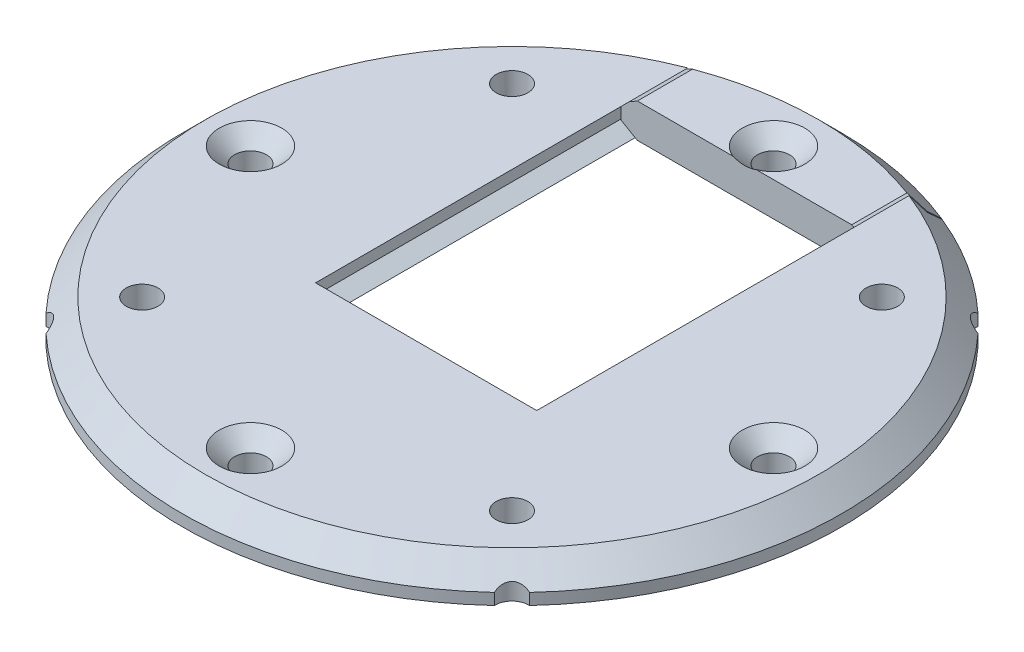
SolidWorks part; units mm, degrees
ref_plane "Front Plane" through (0, 0, 0) normal (0, 0, 1) x (1, 0, 0)
ref_plane "Top Plane" through (0, 0, 0) normal (0, 1, 0) x (1, 0, 0)
ref_plane "Right Plane" through (0, 0, 0) normal (1, 0, 0) x (0, 0, -1)
sketch "Sketch1" plane through (0, 0, 0) normal (0, 1, 0) x (1, 0, 0)
  circle A0 centre (0, 0) radius 29
  dimension "D1" = 58
extrude "Boss-Extrude1" add sketch "Sketch1" along normal mid plane 3
sketch "Sketch2" plane through (0, 1.5, 0) normal (0, 1, 0) x (1, 0, 0)
  line L0 (-11.025, 7.55) -> (-11.025, 29)
  line L1 (-11.025, -7.55) -> (11.025, -7.55)
  line L2 (-11.025, -7.55) -> (-11.025, 7.55)
  line L3 (-11.025, 7.55) -> (11.025, 7.55) construction
  line L4 (11.025, -7.55) -> (11.025, 7.55)
  line L5 (-11.025, -7.55) -> (11.025, 7.55) construction
  line L6 (-11.025, 7.55) -> (11.025, -7.55) construction
  line L7 (-11.025, 29) -> (11.025, 29)
  line L8 (11.025, 29) -> (11.025, 7.55)
  circle A0 centre (0, 0) radius 29 construction
  point P0 (0, 0)
  dimension "D1" = 7.55
  dimension "D2" = 22.05
extrude "Cut-Extrude1" cut sketch "Sketch2" against normal through all
sketch "Sketch3" plane through (0, 0, 7.55) normal (0, 0, -1) x (-1, 0, 0)
  line L0 (0, -1.5) -> (0, 1.5) construction
  line L1 (11.025, -1.5) -> (-11.025, -1.5) construction
  line L2 (11.025, 1.5) -> (-11.025, 1.5) construction
  line L3 (-11.525, -1.5) -> (-9.726, -1.5)
  line L5 (-9.726, -1.5) -> (-11.025, -0.75)
  line L6 (-11.025, -1.5) -> (-11.025, 1.5) construction
  line L7 (-11.025, -0.75) -> (-11.025, 0.75)
  line L8 (-11.025, 0.75) -> (-9.726, 1.5)
  line L9 (-9.726, 1.5) -> (-11.525, 1.5)
  line L10 (29, 1.5) -> (-29, 1.5) construction
  line L11 (-11.525, 1.5) -> (-11.525, -1.5)
  line L12 (-29, -1.5) -> (29, -1.5) construction
  line L13 (-11.025, -1.5) -> (-11.025, 1.5) construction
  line L21 (11.525, 1.5) -> (11.525, -1.5)
  line L22 (9.726, 1.5) -> (11.525, 1.5)
  line L23 (11.025, 0.75) -> (9.726, 1.5)
  line L24 (11.025, -0.75) -> (11.025, 0.75)
  line L25 (9.726, -1.5) -> (11.025, -0.75)
  line L26 (11.525, -1.5) -> (9.726, -1.5)
  point P10 (-11.025, 0)
  dimension "D1" = 0.5
  dimension "D2" = 60
  dimension "D3" = 1.5
extrude "Boss-Extrude2" add sketch "Sketch3" along normal up to surface (34.1615 mm away) up to face at (0, 0, 1.0887)
ref_plane "Plane1" through (0, 0, -20.45) normal (0, 0, -1) x (-1, 0, 0)
sketch "Sketch6" plane through (0, 0, -20.45) normal (0, 0, -1) x (-1, 0, 0)
  line L0 (-9.726, -1.5) -> (-11.025, -0.75) construction
  line L1 (-11.025, -0.75) -> (-11.025, 0.75) construction
  line L2 (-11.025, 0.75) -> (-9.726, 1.5) construction
  line L3 (-9.726, -1.5) -> (-11.025, -0.75) construction
  line L4 (-11.025, -0.75) -> (-11.025, 0.75) construction
  line L5 (-11.025, 0.75) -> (-9.726, 1.5) construction
  line L6 (-9.426, 1.5) -> (-10.875, 0.6634)
  line L7 (9.726, 1.5) -> (-9.726, 1.5) construction
  line L8 (-10.875, 0.6634) -> (-10.875, -0.6634)
  line L9 (-10.875, -0.6634) -> (-9.426, -1.5)
  line L10 (9.726, -1.5) -> (-9.726, -1.5) construction
  line L11 (0, 0) -> (0, 1.5) construction
  line L12 (10.875, -0.6634) -> (9.426, -1.5)
  line L13 (10.875, 0.6634) -> (10.875, -0.6634)
  line L14 (9.426, 1.5) -> (10.875, 0.6634)
  line L15 (-10.875, 0.6634) -> (-10.95, 0.7933) construction
  line L16 (-10.875, 0.6634) -> (-11.025, 0.6634) construction
  line L17 (10.875, -0.6634) -> (9.426, -1.5)
  line L18 (10.875, 0.6634) -> (10.875, -0.6634)
  line L19 (9.426, 1.5) -> (10.875, 0.6634)
  line L20 (-9.426, 1.5) -> (9.426, 1.5)
  line L21 (9.426, -1.5) -> (-9.426, -1.5)
  dimension "D1" = 0.15
extrude "Boss-Extrude3" add sketch "Sketch6" along normal up to surface (6.4337 mm away) separate body contours L21 L12 L13 L14 L20 L6 L8 L9 region at (0, 0, -20.45) up to face at (0, 0, -12.9953)
chamfer "Chamfer1" distance 2 angle 45 1 edges at (0, 1.5, 29)
chamfer "Chamfer2" distance 2 angle 45 2 edges at (-4.7783, 1.5, -28.6036) (4.7783, 1.5, -28.6036)
sketch "Sketch5" plane through (0, 1.5, 0) normal (0, 1, 0) x (1, 0, 0)
  circle A0 centre (0, 0) radius 23 construction
  circle A1 centre (0, 23) radius 1.4
  circle A2 centre (16.2635, 16.2635) radius 1.4
  circle A3 centre (23, 0) radius 1.4
  circle A4 centre (16.2635, -16.2635) radius 1.4
  circle A5 centre (0, -23) radius 1.4
  circle A6 centre (-16.2635, -16.2635) radius 1.4
  circle A7 centre (-23, 0) radius 1.4
  circle A8 centre (-16.2635, 16.2635) radius 1.4
  point P21 (0, 0)
  dimension "D1" = 46
  dimension "D2" = 2.8
  dimension "D3" = 8
extrude "Cut-Extrude2" cut sketch "Sketch5" against normal through all
hole_wizard "CSK for M2.5 Flat Head Machine Screw1" positions "Sketch7" profile "Sketch8" countersink size "M2.5" standard "ANSI Metric" end condition through all
sketch "Sketch7" plane through (0, 1.5, 0) normal (0, 1, 0) x (1, 0, 0)
  point P13 (0, 23)
  point P16 (23, 0)
  point P19 (0, -23)
  point P22 (-23, 0)
  point P26 (0, 0)
  point P27 (0, 0)
  point P28 (0, 0)
  point P29 (0, 0)
sketch "Sketch8" plane through (0, 1.5, -23) normal (1, 0, 0) x (0, 0, 1)
  line L0 (0, 0) -> (0, 3)
  line L1 (0, 3) -> (1.35, 3)
  line L2 (1.35, 3) -> (1.35, 1.4)
  line L3 (1.35, 1.4) -> (2.75, 0)
  line L5 (2.75, 0) -> (0, 0)
  line L6 (-1.35, 1.4) -> (-2.75, 0) construction
  line L11 (0, -6.35) -> (0, 107.95) construction
  dimension "Thru Hole Dia." = 2.7
  dimension "Thru Hole Depth" = 3
  dimension "Near C'Sink Dia." = 5.5
  dimension "Near C'Sink Angle" = 90
sketch "Sketch10" [suppressed] plane through (0, 1.5, 0) normal (0, 1, 0) x (1, 0, 0)
  line L0 (0, 0) -> (0, -30) construction
  line L1 (15, -12.5) -> (11.5, -12.5) construction
  line L6 (-15, 12.5) -> (-11.5, 12.5) construction
  line L7 (-15, 12.5) -> (-15, -12.5) construction
  line L8 (-15, -12.5) -> (-11.5, -12.5) construction
  line L9 (-11.5, 12.5) -> (-11.5, -12.5) construction
  line L10 (-11.5, -12.5) -> (11.5, -12.5) construction
  line L11 (-11.5, -12.5) -> (-11.5, -9) construction
  line L12 (-11.5, -9) -> (11.5, -9) construction
  line L13 (11.5, -12.5) -> (11.5, -9) construction
  line L14 (11.5, 12.5) -> (11.5, -12.5) construction
  line L15 (15, 12.5) -> (11.5, 12.5) construction
  line L16 (15, 12.5) -> (15, -12.5) construction
  line L17 (0, 0) -> (-11.5, 0) construction
  line L18 (-11.5, -9) -> (-11.5, 12.5)
  line L19 (-11.5, 12.5) -> (-15, 12.5)
  line L20 (-15, 12.5) -> (-15, -12.5)
  line L21 (-15, -12.5) -> (15, -12.5)
  line L22 (15, -12.5) -> (15, 12.5)
  line L23 (15, 12.5) -> (11.5, 12.5)
  line L24 (11.5, 12.5) -> (11.5, -9)
  line L25 (11.5, -9) -> (-11.5, -9)
  arc A0 (-11.025, 27.9007) -> (11.025, 27.9007) centre (0, 0) ccw construction
  point P18 (-11.5, 0)
  point P36 (0, -12.5)
  point P37 (0, -9)
  dimension "D5" = 30
  dimension "D1" = 3.5
  dimension "D2" = 3.5
  dimension "D3" = 23
  dimension "D4" = 25
  dimension "D6" = 25
extrude "Boss-Extrude4" [suppressed] add sketch "Sketch10" along normal blind 5
sketch "Sketch11" [suppressed] plane through (0, 0, 9) normal (0, 0, -1) x (-1, 0, 0)
  line L0 (-11.5, 6.5) -> (11.5, 6.5) construction
  line L1 (0, 6.5) -> (-2.45, 5.0855) construction
  line L2 (-2.45, 5.0855) -> (-2.45, 2.2565)
  line L3 (-2.45, 2.2565) -> (0, 0.842)
  line L4 (0, 0.842) -> (2.45, 2.2565)
  line L5 (2.45, 2.2565) -> (2.45, 5.0855)
  line L6 (2.45, 5.0855) -> (0, 6.5) construction
  line L7 (-2.45, 5.0855) -> (-2.45, 6.5)
  line L8 (-2.45, 6.5) -> (2.45, 6.5)
  line L9 (2.45, 6.5) -> (2.45, 5.0855)
  circle A0 centre (0, 3.671) radius 2.45 construction
  dimension "D1" = 4.9
extrude "Cut-Extrude3" [suppressed] cut sketch "Sketch11" against normal blind 2
chamfer "Chamfer3" [suppressed] distance 3.5 angle 45
sketch "Sketch12" [suppressed] plane through (-11.5, 0, 0) normal (1, 0, 0) x (0, 0, -1)
  line L0 (0, 0) -> (0, 6.5) construction
  line L1 (-9, 6.5) -> (9, 6.5) construction
  line L2 (-9, 5.0855) -> (-9, 6.5)
  line L3 (-6.55, 6.5) -> (-9, 5.0855) construction
  line L4 (-9, 5.0855) -> (-9, 2.2565)
  line L5 (-9, 2.2565) -> (-6.55, 0.842)
  line L6 (-6.55, 0.842) -> (-4.1, 2.2565)
  line L7 (-4.1, 2.2565) -> (-4.1, 5.0855)
  line L8 (-4.1, 5.0855) -> (-6.55, 6.5) construction
  line L9 (-9, 6.5) -> (-4.1, 6.5)
  line L10 (-4.1, 6.5) -> (-4.1, 5.0855)
  line L11 (9, 6.5) -> (4.1, 6.5)
  line L12 (9, 5.0855) -> (9, 6.5)
  line L13 (9, 5.0855) -> (9, 2.2565)
  line L14 (9, 2.2565) -> (6.55, 0.842)
  line L15 (6.55, 0.842) -> (4.1, 2.2565)
  line L16 (4.1, 2.2565) -> (4.1, 5.0855)
  line L17 (4.1, 6.5) -> (4.1, 5.0855)
  line L18 (-9, 6.5) -> (-9, 1.5) construction
  circle A0 centre (-6.55, 3.671) radius 2.45 construction
  dimension "D2" = 4.9
extrude "Cut-Extrude4" [suppressed] cut sketch "Sketch12" against normal blind 2
mirror "Mirror1" [suppressed] about plane through (0, 0, 0) normal (1, 0, 0)
sketch "Sketch13" [suppressed] plane through (0, 0, 11) normal (0, 0, -1) x (-1, 0, 0)
  circle A0 centre (0, 3.671) radius 1.4
  dimension "D1" = 2.8
extrude "Cut-Extrude5" [suppressed] cut sketch "Sketch13" against normal blind 2
sketch "Sketch14" [suppressed] plane through (-15, 0, 0) normal (-1, 0, 0) x (0, 0, 1)
  line L0 (0, 6.5) -> (0, 0) construction
  line L1 (-9, 6.5) -> (9, 6.5) construction
  circle A0 centre (6.55, 3.671) radius 1.4
  circle A1 centre (-6.55, 3.671) radius 1.4
  dimension "D1" = 2.8
extrude "Cut-Extrude6" [suppressed] cut sketch "Sketch14" against normal through all both and the other way through all
sketch "Sketch15" plane through (0, 0, 0) normal (0, 1, 0) x (1, 0, 0)
  line L0 (0, 0) -> (-20.5061, 20.5061) construction
  line L1 (0, 0) -> (0, -29) construction
  arc A0 (-11.025, 26.8226) -> (11.025, 26.8226) centre (0, 0) ccw construction
  circle A1 centre (-21.2132, 21.2132) radius 1.5
  circle A2 centre (21.2132, 21.2132) radius 1.5
  circle A3 centre (21.2132, -21.2132) radius 1.5
  circle A4 centre (-21.2132, -21.2132) radius 1.5
  point P17 (0, 0)
  dimension "D2" = 3
  dimension "D1" = 135
  dimension "D3" = 1
  dimension "D4" = 4
extrude "Cut-Extrude7" cut sketch "Sketch15" against normal through all
equation "\"m2.5 width\"= 4.9mm"
equation "\"D1@Sketch11\"=\"m2.5 width\""
equation "\"D2@Sketch12\"=\"m2.5 width\""
